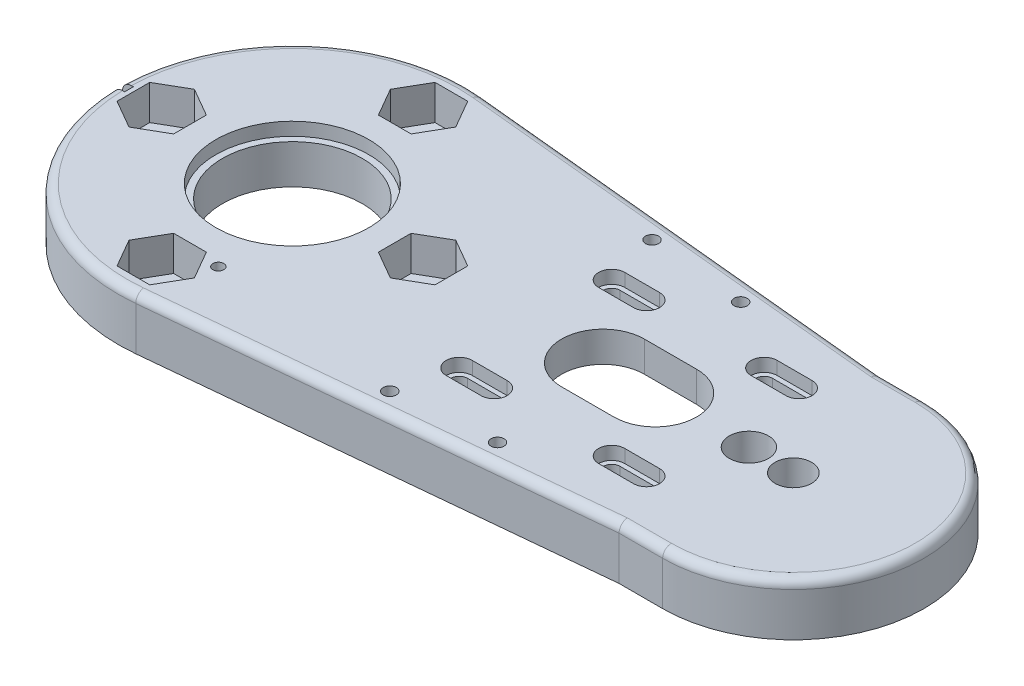
SolidWorks part; units mm, degrees
ref_plane "Front Plane" through (0, 0, 0) normal (0, 0, 1) x (1, 0, 0)
ref_plane "Top Plane" through (0, 0, 0) normal (0, 1, 0) x (1, 0, 0)
ref_plane "Right Plane" through (0, 0, 0) normal (1, 0, 0) x (0, 0, -1)
sketch "Sketch1" plane through (0, 0, 0) normal (0, 1, 0) x (1, 0, 0)
  line L0 (3.8629, 39.813) -> (105, 30)
  line L1 (105, 30) -> (105, -30)
  line L2 (105, -30) -> (3.8629, -39.813)
  arc A0 (3.8629, 39.813) -> (3.8629, -39.813) centre (0, 0) ccw
  circle A1 centre (0, 0) radius 10
  point P4 (105, 0)
  dimension "D1" = 40
  dimension "D4" = 20
  dimension "D2" = 60
  dimension "D3" = 105
extrude "Boss-Extrude1" add sketch "Sketch1" along normal blind 12
sketch "Sketch2" plane through (0, 12, 0) normal (0, 1, 0) x (1, 0, 0)
  circle A0 centre (0, 0) radius 17.55
  dimension "D1" = 35.1
extrude "Cut-Extrude1" cut sketch "Sketch2" against normal blind 3
sketch "Sketch3" plane through (0, 12, 0) normal (0, 1, 0) x (1, 0, 0)
  line L0 (71.3, 0) -> (83.3, 0) construction
  line L1 (71.3, 9.5) -> (83.3, 9.5)
  line L2 (71.3, -9.5) -> (83.3, -9.5)
  arc A0 (71.3, 9.5) -> (71.3, -9.5) centre (71.3, 0) ccw
  arc A1 (83.3, -9.5) -> (83.3, 9.5) centre (83.3, 0) ccw
  point P3 (77.3, 0)
  dimension "D1" = 19
  dimension "D2" = 12
  dimension "D3" = 77.3
extrude "Cut-Extrude2" cut sketch "Sketch3" against normal up to surface (12 mm away) up to face at (43.4657, 0, 0)
sketch "Sketch4" plane through (0, 12, 0) normal (0, 1, 0) x (1, 0, 0)
  circle A0 centre (30, 0) radius 4
  circle A1 centre (0, -30) radius 4
  circle A2 centre (-30, 0) radius 4
  circle A3 centre (0, 30) radius 4
  point P12 (0, 0)
  dimension "D2" = 8
  dimension "D1" = 30
  dimension "D3" = 4
extrude "Cut-Extrude3" cut sketch "Sketch4" against normal up to surface (12 mm away) up to face at (77.3, 0, 0)
sketch "Sketch5" plane through (0, 9, 0) normal (0, -1, 0) x (1, 0, 0)
  circle A0 centre (0, 0) radius 16.05
  dimension "D1" = 32.1
extrude "Cut-Extrude4" cut sketch "Sketch5" along normal through all
sketch "Sketch6" plane through (0, 0, 0) normal (0, -1, 0) x (1, 0, 0)
  line L0 (71.3, 9.5) -> (83.3, -9.5) construction
  line L1 (49.8, 22.65) -> (104.8, 22.65)
  line L2 (49.8, 22.65) -> (49.8, -22.65)
  line L3 (49.8, -22.65) -> (104.8, -22.65)
  line L4 (104.8, 22.65) -> (104.8, -22.65)
  line L5 (49.8, 22.65) -> (104.8, -22.65) construction
  line L6 (49.8, -22.65) -> (104.8, 22.65) construction
  line L7 (92.8, 0) -> (95.8, 0)
  line L10 (61.8, 0) -> (58.8, 0)
  arc A0 (83.3, -9.5) -> (83.3, 9.5) centre (83.3, 0) ccw construction
  arc A1 (71.3, 9.5) -> (71.3, -9.5) centre (71.3, 0) ccw construction
  point P0 (77.3, 0)
  point P9 (77.3, 0)
  dimension "D1" = 45.3
  dimension "D2" = 55
  dimension "D3" = 3
  dimension "D6" = 3
sketch "Sketch7" plane through (0, 12, 0) normal (0, 1, 0) x (1, 0, 0)
  line L24 (-7.5056, 30) -> (-3.7528, 23.5)
  line L25 (-30, -7.5056) -> (-23.5, -3.7528)
  line L26 (-23.5, -3.7528) -> (-23.5, 3.7528)
  line L27 (-23.5, 3.7528) -> (-30, 7.5056)
  line L28 (-30, 7.5056) -> (-36.5, 3.7528)
  line L29 (-36.5, 3.7528) -> (-36.5, -3.7528)
  line L30 (-36.5, -3.7528) -> (-30, -7.5056)
  line L31 (-3.7528, 23.5) -> (3.7528, 23.5)
  line L32 (3.7528, 23.5) -> (7.5056, 30)
  line L33 (7.5056, 30) -> (3.7528, 36.5)
  line L34 (3.7528, 36.5) -> (-3.7528, 36.5)
  line L35 (-3.7528, 36.5) -> (-7.5056, 30)
  line L36 (30, 7.5056) -> (23.5, 3.7528)
  line L37 (23.5, 3.7528) -> (23.5, -3.7528)
  line L38 (23.5, -3.7528) -> (30, -7.5056)
  line L39 (30, -7.5056) -> (36.5, -3.7528)
  line L40 (36.5, -3.7528) -> (36.5, 3.7528)
  line L41 (36.5, 3.7528) -> (30, 7.5056)
  line L42 (7.5056, -30) -> (3.7528, -23.5)
  line L43 (3.7528, -23.5) -> (-3.7528, -23.5)
  line L44 (-3.7528, -23.5) -> (-7.5056, -30)
  line L45 (-7.5056, -30) -> (-3.7528, -36.5)
  line L46 (-3.7528, -36.5) -> (3.7528, -36.5)
  line L47 (3.7528, -36.5) -> (7.5056, -30)
  circle A4 centre (-30, 0) radius 6.5 construction
  point P12 (0, 0)
  point P30 (0, 0)
  point P32 (0, 0)
  dimension "D1" = 13
  dimension "D2" = 4
extrude "Cut-Extrude6" cut sketch "Sketch7" against normal blind 8
sketch "Sketch9" plane through (0, 12, 0) normal (0, 1, 0) x (1, 0, 0)
  line L0 (55.8, 17.5) -> (63.8, 17.5) construction
  line L1 (55.8, 20.5) -> (63.8, 20.5)
  line L2 (55.8, 14.5) -> (63.8, 14.5)
  line L3 (90.8, 17.5) -> (98.8, 17.5) construction
  line L4 (90.8, 20.5) -> (98.8, 20.5)
  line L5 (90.8, 14.5) -> (98.8, 14.5)
  line L6 (55.8, -17.5) -> (63.8, -17.5) construction
  line L7 (55.8, -14.5) -> (63.8, -14.5)
  line L8 (55.8, -20.5) -> (63.8, -20.5)
  line L9 (90.8, -17.5) -> (98.8, -17.5) construction
  line L10 (90.8, -14.5) -> (98.8, -14.5)
  line L11 (90.8, -20.5) -> (98.8, -20.5)
  line L12 (59.8, -17.5) -> (94.8, 17.5) construction
  line L13 (59.8, 17.5) -> (94.8, -17.5) construction
  line L14 (71.3, 9.5) -> (83.3, -9.5) construction
  arc A0 (55.8, 20.5) -> (55.8, 14.5) centre (55.8, 17.5) ccw
  arc A1 (63.8, 14.5) -> (63.8, 20.5) centre (63.8, 17.5) ccw
  arc A2 (90.8, 20.5) -> (90.8, 14.5) centre (90.8, 17.5) ccw
  arc A3 (98.8, 14.5) -> (98.8, 20.5) centre (98.8, 17.5) ccw
  arc A4 (55.8, -14.5) -> (55.8, -20.5) centre (55.8, -17.5) ccw
  arc A5 (63.8, -20.5) -> (63.8, -14.5) centre (63.8, -17.5) ccw
  arc A6 (90.8, -14.5) -> (90.8, -20.5) centre (90.8, -17.5) ccw
  arc A7 (98.8, -20.5) -> (98.8, -14.5) centre (98.8, -17.5) ccw
  point P2 (59.8, 17.5)
  point P8 (94.8, 17.5)
  point P15 (59.8, -17.5)
  point P22 (94.8, -17.5)
  point P36 (77.3, 0)
  point P37 (77.3, 0)
  dimension "D1" = 6
  dimension "D2" = 6
  dimension "D3" = 8
  dimension "D4" = 8
  dimension "D5" = 8
  dimension "D6" = 8
  dimension "D7" = 6
  dimension "D8" = 6
  dimension "D9" = 35
  dimension "D10" = 35
extrude "Cut-Extrude7" cut sketch "Sketch9" against normal blind 3
sketch "Sketch10" plane through (0, 9, 0) normal (0, 1, 0) x (1, 0, 0)
  line L4 (55.8, 15.6) -> (63.8, 15.6)
  line L5 (63.8, 19.4) -> (55.8, 19.4)
  line L6 (55.8, 15.6) -> (63.8, 15.6)
  line L7 (63.8, 19.4) -> (55.8, 19.4)
  line L10 (90.8, 15.6) -> (98.8, 15.6)
  line L11 (98.8, 19.4) -> (90.8, 19.4)
  line L12 (90.8, 15.6) -> (98.8, 15.6)
  line L13 (98.8, 19.4) -> (90.8, 19.4)
  line L16 (55.8, -19.4) -> (63.8, -19.4)
  line L17 (63.8, -15.6) -> (55.8, -15.6)
  line L18 (55.8, -19.4) -> (63.8, -19.4)
  line L19 (63.8, -15.6) -> (55.8, -15.6)
  line L22 (90.8, -19.4) -> (98.8, -19.4)
  line L23 (98.8, -15.6) -> (90.8, -15.6)
  line L24 (90.8, -19.4) -> (98.8, -19.4)
  line L25 (98.8, -15.6) -> (90.8, -15.6)
  arc A2 (98.8, 15.6) -> (98.8, 19.4) centre (98.8, 17.5) ccw
  arc A3 (98.8, 15.6) -> (98.8, 19.4) centre (98.8, 17.5) ccw
  arc A4 (55.8, 19.4) -> (55.8, 15.6) centre (55.8, 17.5) ccw
  arc A5 (63.8, 15.6) -> (63.8, 19.4) centre (63.8, 17.5) ccw
  arc A6 (55.8, 19.4) -> (55.8, 15.6) centre (55.8, 17.5) ccw
  arc A7 (63.8, 15.6) -> (63.8, 19.4) centre (63.8, 17.5) ccw
  arc A8 (98.8, -19.4) -> (98.8, -15.6) centre (98.8, -17.5) ccw
  arc A9 (98.8, -19.4) -> (98.8, -15.6) centre (98.8, -17.5) ccw
  arc A10 (90.8, 19.4) -> (90.8, 15.6) centre (90.8, 17.5) ccw
  arc A12 (90.8, 19.4) -> (90.8, 15.6) centre (90.8, 17.5) ccw
  arc A16 (55.8, -15.6) -> (55.8, -19.4) centre (55.8, -17.5) ccw
  arc A17 (63.8, -19.4) -> (63.8, -15.6) centre (63.8, -17.5) ccw
  arc A18 (55.8, -15.6) -> (55.8, -19.4) centre (55.8, -17.5) ccw
  arc A19 (63.8, -19.4) -> (63.8, -15.6) centre (63.8, -17.5) ccw
  arc A22 (90.8, -15.6) -> (90.8, -19.4) centre (90.8, -17.5) ccw
  arc A24 (90.8, -15.6) -> (90.8, -19.4) centre (90.8, -17.5) ccw
  dimension "D2" = 1.1
  dimension "D1" = 1.1
  dimension "D3" = 1.1
  dimension "D4" = 1.1
sketch "Sketch11" plane through (0, 12, 0) normal (0, 1, 0) x (1, 0, 0)
  line L0 (105, -30) -> (105, 30)
  line L1 (105, -30) -> (105, 30) construction
  line L2 (105, 30) -> (115, 30)
  line L3 (115, -30) -> (105, -30)
  arc A0 (115, 30) -> (115, -30) centre (115, 0) cw
  circle A1 centre (115, 0) radius 4.2
  point P7 (105, 0)
  point P8 (105, 0)
  dimension "D1" = 60
  dimension "D3" = 8.4
  dimension "D2" = 10
extrude "Boss-Extrude2" add sketch "Sketch11" against normal up to surface (12 mm away) up to face at (0, 0, -16.05)
extrude "切除-拉伸1" cut sketch "Sketch10" against normal through all
sketch "草图1" plane through (0, 12, 0) normal (0, 1, 0) x (1, 0, 0)
  line L0 (92.8, 0) -> (104.8, 0)
  arc A2 (83.3, -9.5) -> (83.3, 9.5) centre (83.3, 0) ccw construction
  circle A3 centre (104.8, 0) radius 4.5
  dimension "D1" = 12
extrude "切除-拉伸4" cut sketch "草图1" against normal through all
sketch "草图2" plane through (0, 12, 0) normal (0, 1, 0) x (1, 0, 0)
  line L0 (0, 0) -> (45, 0) construction
  line L1 (45, 0) -> (45, -13.75) construction
  line L2 (45, 0) -> (45, 13.75) construction
  circle A0 centre (45, -13.75) radius 2.5
  circle A1 centre (45, 13.75) radius 2.5
  dimension "D1" = 5
sketch "草图3" plane through (0, 12, 0) normal (0, 1, 0) x (1, 0, 0)
  circle A0 centre (45, -13.75) radius 6
  circle A1 centre (45, 13.75) radius 6
extrude "切除-拉伸6" cut sketch "Sketch6" against normal blind 5
sketch "草图5" plane through (0, 12, 0) normal (0, 1, 0) x (1, 0, 0)
  line L0 (0, 23.5) -> (0, 25) construction
  line L1 (-3.7528, 23.5) -> (3.7528, 23.5) construction
  circle A0 centre (0, 25) radius 2
  dimension "D1" = 1.5
sketch "草图6" plane through (0, 12, 0) normal (0, 1, 0) x (1, 0, 0)
  circle A0 centre (8, -25) radius 1.25
  dimension "D1" = 2.5
extrude "切除-拉伸9" cut sketch "草图6" against normal blind 3
sketch "草图7" plane through (0, 0, 0) normal (0, -1, 0) x (1, 0, 0)
  circle A0 centre (75, -27.9108) radius 1.5
  circle A1 centre (75, 27.9108) radius 1.5
  circle A2 centre (75, -27.9108) radius 1.5 construction
  circle A3 centre (75, -27.9108) radius 1.5 construction
  circle A4 centre (75, 27.9108) radius 1.5 construction
  circle A5 centre (52.4604, -30.0978) radius 1.5
  circle A6 centre (52.4604, 30.0978) radius 1.5
  circle A7 centre (52.4604, 30.0978) radius 1.5 construction
  circle A11 centre (52.4604, -30.0978) radius 1.5 construction
extrude "切除-拉伸10" cut sketch "草图7" against normal through all
sketch "草图4" plane through (0, 0, 0) normal (0, -1, 0) x (1, 0, 0)
  line L0 (75, 24.7354) -> (77.75, 26.3231)
  line L1 (77.75, 26.3231) -> (77.75, 29.4985)
  line L2 (77.75, 29.4985) -> (75, 31.0862)
  line L3 (75, 31.0862) -> (72.25, 29.4985)
  line L4 (72.25, 29.4985) -> (72.25, 26.3231)
  line L5 (72.25, 26.3231) -> (75, 24.7354)
  line L6 (75, -31.0862) -> (77.75, -29.4985)
  line L7 (77.75, -29.4985) -> (77.75, -26.3231)
  line L8 (77.75, -26.3231) -> (75, -24.7354)
  line L9 (75, -24.7354) -> (72.25, -26.3231)
  line L10 (72.25, -26.3231) -> (72.25, -29.4985)
  line L11 (72.25, -29.4985) -> (75, -31.0862)
  line L12 (52.4604, 26.9223) -> (55.2104, 28.5101)
  line L13 (55.2104, 28.5101) -> (55.2104, 31.6855)
  line L14 (55.2104, 31.6855) -> (52.4604, 33.2732)
  line L15 (52.4604, 33.2732) -> (49.7104, 31.6855)
  line L16 (49.7104, 31.6855) -> (49.7104, 28.5101)
  line L17 (49.7104, 28.5101) -> (52.4604, 26.9223)
  line L18 (52.4604, -33.2732) -> (55.2104, -31.6855)
  line L19 (55.2104, -31.6855) -> (55.2104, -28.5101)
  line L20 (55.2104, -28.5101) -> (52.4604, -26.9223)
  line L21 (52.4604, -26.9223) -> (49.7104, -28.5101)
  line L22 (49.7104, -28.5101) -> (49.7104, -31.6855)
  line L23 (49.7104, -31.6855) -> (52.4604, -33.2732)
  circle A0 centre (75, 27.9108) radius 2.75 construction
  circle A1 centre (75, -27.9108) radius 2.75 construction
  circle A2 centre (75, -27.9108) radius 1.5 construction
  circle A3 centre (75, 27.9108) radius 1.5 construction
  circle A4 centre (52.4604, 30.0978) radius 2.75 construction
  circle A5 centre (52.4604, -30.0978) radius 2.75 construction
  circle A8 centre (52.4604, -30.0978) radius 1.5 construction
  circle A9 centre (52.4604, 30.0978) radius 1.5 construction
  dimension "D1" = 5.5
  dimension "D2" = 5.5
  dimension "D3" = 5.5
  dimension "D4" = 5.5
extrude "切除-拉伸11" cut sketch "草图4" against normal blind 2.5
fillet "圆角1" radius 2 3 edges at (54.4315, 12, 34.9065) (-40, 12, 0) (54.4315, 12, -34.9065)
fillet "圆角2" radius 2 3 edges at (99.6452, 12, 30) (99.6452, 12, -30) (145, 12, 0)
ref_plane "基准面1" through (-40, 0, 0) normal (-1, 0, 0) x (0, 0, 1)
sketch "草图8" plane through (-40, 0, 0) normal (-1, 0, 0) x (0, 0, 1)
  line L0 (40, 10) -> (-40, 10) construction
  line L1 (-1, 12) -> (1, 12)
  line L2 (-1, 12) -> (-1, 4.8023)
  line L3 (-1, 4.8023) -> (1, 4.8023)
  line L4 (1, 12) -> (1, 4.8023)
  line L5 (0, 12) -> (13.75, 12) construction
  point P4 (0, 10)
  point P5 (0, 12)
  point P8 (0, 0)
  point P9 (0.5432, 12)
  dimension "D1" = 2
extrude "切除-拉伸12" cut sketch "草图8" against normal blind 2.5 contours L4 L3 L2 L1
